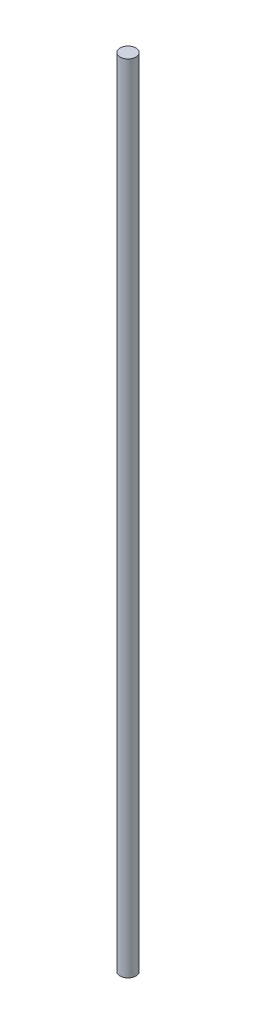
SolidWorks part; units mm, degrees
material "Thornel Mat VMA"
ref_plane "前视基准面" through (0, 0, 0) normal (0, 0, 1) x (1, 0, 0)
ref_plane "上视基准面" through (0, 0, 0) normal (0, 1, 0) x (1, 0, 0)
ref_plane "右视基准面" through (0, 0, 0) normal (1, 0, 0) x (0, 0, -1)
sketch "草图1" plane through (0, 0, 0) normal (0, 1, 0) x (1, 0, 0)
  circle A0 centre (0, 0) radius 0.75
  dimension "D1" = 1.5
extrude "凸台-拉伸1" add sketch "草图1" along normal blind 75
equation "\"m\"= 2"
